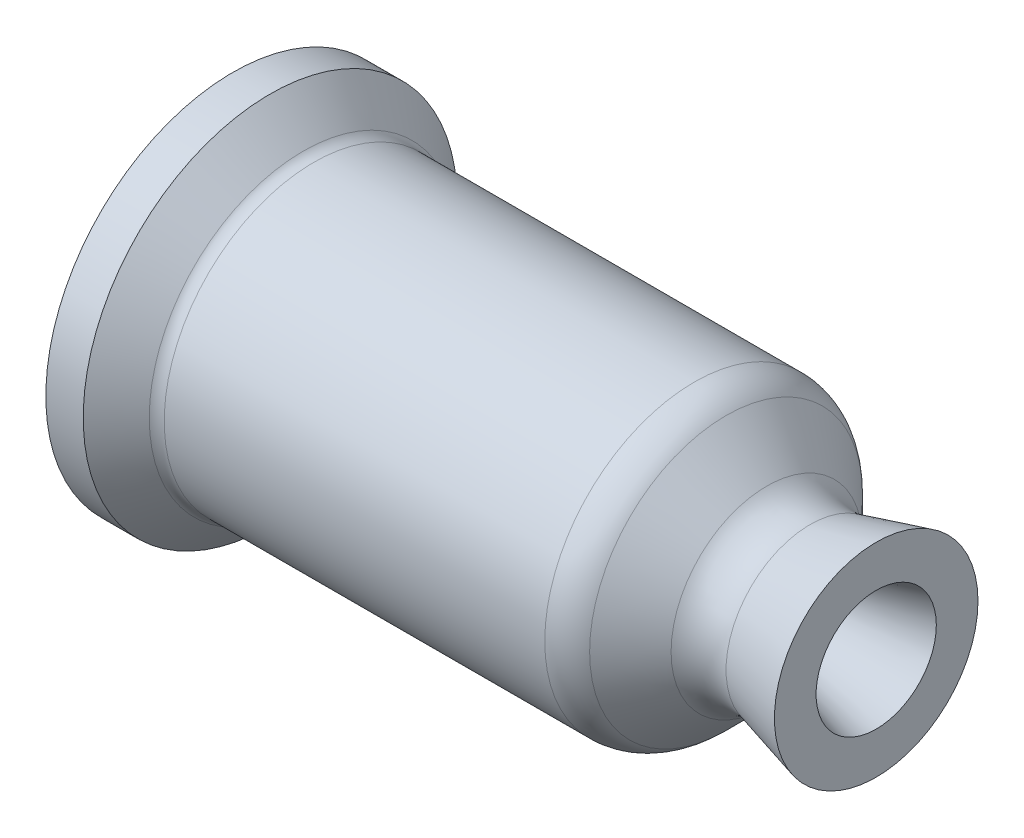
SolidWorks part; units mm, degrees
material "Cast Carbon Steel"
ref_plane "Front Plane" through (0, 0, 0) normal (0, 0, 1) x (1, 0, 0)
ref_plane "Top Plane" through (0, 0, 0) normal (0, 1, 0) x (1, 0, 0)
ref_plane "Right Plane" through (0, 0, 0) normal (1, 0, 0) x (0, 0, -1)
sketch "Sketch1" plane through (0, 0, 0) normal (0, 0, 1) x (1, 0, 0)
  line L0 (0, 0) -> (0, 18.564) construction
  line L1 (0, 18.564) -> (78.7, 18.564)
  line L2 (78.7, 18.564) -> (91.076, 6.188)
  line L3 (91.076, 6.188) -> (94.251, 6.188)
  line L4 (94.251, 6.188) -> (109.2576, 10.209)
  line L5 (109.2576, 10.209) -> (109.2576, 25.4)
  line L6 (109.2576, 25.4) -> (0, 25.4)
  line L7 (0, 25.4) -> (0, 18.564)
  line L8 (81.5316, 25.4) -> (93.79, 13.1416)
  line L10 (93.79, 13.1416) -> (109.2576, 17.2861)
  line L11 (22.3107, 25.4) -> (22.3107, 18.564) construction
  line L12 (85.1789, 21.7527) -> (80.3451, 16.9189) construction
  line L13 (103.3519, 15.7037) -> (105.1212, 9.1007) construction
  line L14 (0, 0) -> (-20.4849, 0) construction
  line L15 (6.35, 31.75) -> (12.7, 25.4)
  line L16 (0, 25.4) -> (0, 31.75)
  line L17 (0, 31.75) -> (6.35, 31.75)
  line L18 (6.35, 31.75) -> (6.35, 25.4)
  dimension "D1" = 18.564
  dimension "D2" = 25.4
  dimension "D3" = 6.188
  dimension "D4" = 135
  dimension "D5" = 165
  dimension "D6" = 3.175
  dimension "D7" = 10.209
  dimension "D8" = 78.7
  dimension "D9" = 6.35
  dimension "D10" = 135
  dimension "D11" = 6.35
revolve "Revolve1" add sketch "Sketch1" angle 360 about L14 region at (56.2626, 19.4644, 0) region at (3.175, 28.575, 0) region at (8.4667, 27.5167, 0)
fillet "Fillet8" radius 7.62 3 edges at (78.7, 0, -18.564) (81.5316, 0, -25.4) (93.79, 0, -13.1416)
fillet "Fillet9" radius 2.54 1 edges at (12.7, 0, -25.4)
sketch "Sketch2" plane through (0, 0, 0) normal (-1, 0, 0) x (0, 0, 1)
  circle A0 centre (0, 0) radius 28.1781
  circle A1 centre (0, 0) radius 29.7656
  dimension "D1" = 1.5875
  dimension "D2" = 56.3562
extrude "Cut-Extrude1" cut sketch "Sketch2" against normal blind 1.3335
